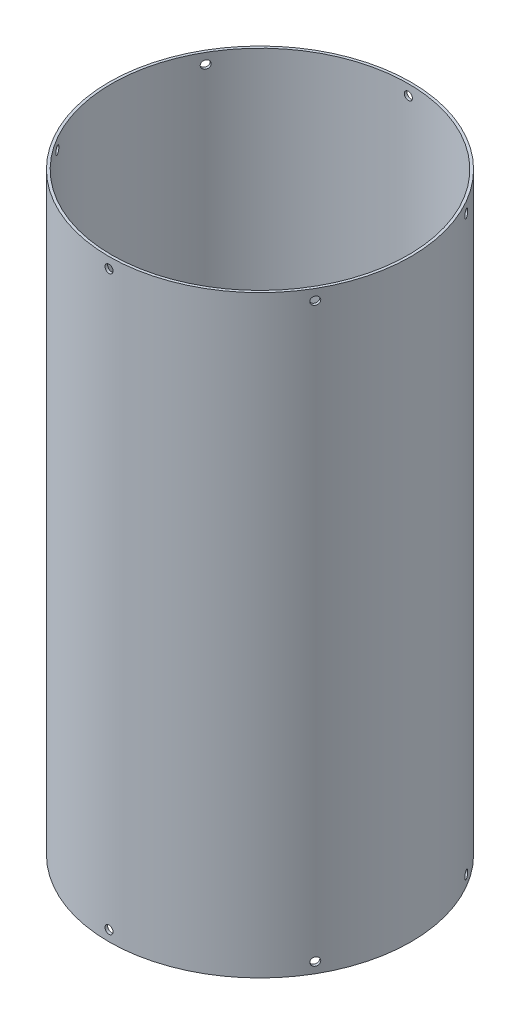
SolidWorks part; units mm, degrees
material "A-Glass Fiber"
ref_plane "Front Plane" through (0, 0, 0) normal (0, 0, 1) x (1, 0, 0)
ref_plane "Top Plane" through (0, 0, 0) normal (0, 1, 0) x (1, 0, 0)
ref_plane "Right Plane" through (0, 0, 0) normal (1, 0, 0) x (0, 0, -1)
sketch "Sketch2" plane through (0, 0, 0) normal (0, 1, 0) x (1, 0, 0)
  circle A0 centre (0, 0) radius 88.9
  circle A1 centre (0, 0) radius 90.4875
  dimension "D1" = 177.8
  dimension "D2" = 1.5875
extrude "Boss-Extrude1" add sketch "Sketch2" along normal blind 355.6
sketch "Sketch3" plane through (0, 0, 0) normal (0, 0, 1) x (1, 0, 0)
  line L0 (0, 0) -> (0, 6.35) construction
  line L1 (-90.4875, 0) -> (90.4875, 0) construction
  line L2 (-90.4875, 0) -> (-90.4875, 355.6) construction
  line L3 (-90.4875, 355.6) -> (90.4875, 355.6) construction
  line L4 (90.4875, 0) -> (90.4875, 355.6) construction
  line L5 (0, 6.35) -> (0, 349.25) construction
  line L7 (0, 355.6) -> (0, 349.25) construction
  circle A0 centre (0, 349.25) radius 2.413
  circle A1 centre (0, 6.35) radius 2.413
  dimension "D2" = 4.826
  dimension "D4" = 4.826
  dimension "D1" = 6.35
  dimension "D3" = 6.35
extrude "Cut-Extrude1" cut sketch "Sketch3" against normal through all both and the other way through all
pattern_circular "CirPattern1" count 6 over 360 about axis through (0, 355.6, 0) along (0, 1, 0) of "Cut-Extrude1"
